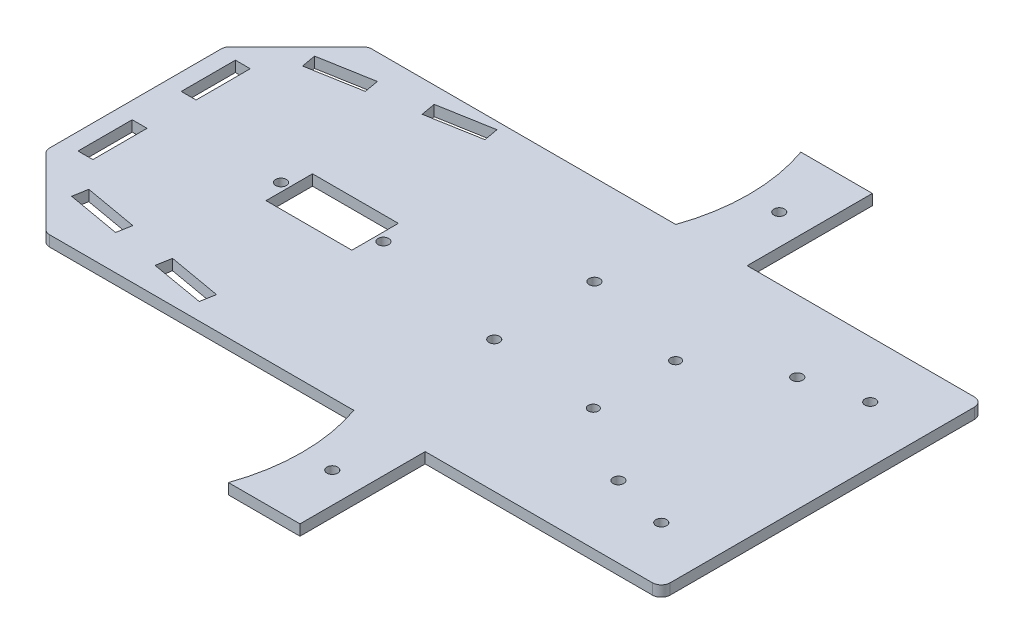
SolidWorks part; units mm, degrees
ref_plane "Front Plane" through (0, 0, 0) normal (0, 0, 1) x (1, 0, 0)
ref_plane "Top Plane" through (0, 0, 0) normal (0, 1, 0) x (1, 0, 0)
ref_plane "Right Plane" through (0, 0, 0) normal (1, 0, 0) x (0, 0, -1)
sketch "Sketch1" plane through (0, 0, 0) normal (0, 1, 0) x (1, 0, 0)
  line L1 (0, 0) -> (192, 0)
  line L2 (0, 0) -> (0, 90)
  line L3 (0, 90) -> (192, 90)
  line L4 (192, 0) -> (192, 90)
  dimension "D1" = 192
  dimension "D2" = 90
extrude "Boss-Extrude1" add sketch "Sketch1" along normal blind 3
sketch "Sketch3" plane through (0, 3, 0) normal (0, 1, 0) x (1, 0, 0)
  line L5 (126, 90) -> (106, 90)
  line L6 (126, 90) -> (126, 125)
  line L7 (126, 125) -> (106, 125)
  line L8 (106, 90) -> (106, 125)
  dimension "D1" = 35
  dimension "D2" = 20
extrude "Boss-Extrude2" add sketch "Sketch3" against normal blind 3
sketch "Sketch4" plane through (0, 3, 0) normal (0, 1, 0) x (1, 0, 0)
  line L2 (106, 125) -> (106, 89.875)
  arc A0 (106, 125) -> (106, 89.875) centre (56.0932, 107.4375) cw
extrude "Cut-Extrude1" cut sketch "Sketch4" against normal blind 5
ref_plane "Plane1" through (0, 0, -45) normal (0, 0, 1) x (1, 0, 0)
mirror "Mirror1" about plane through (0, 0, -45) normal (0, 0, 1) of "Cut-Extrude1", "Boss-Extrude2"
sketch "Sketch5" plane through (0, 3, 0) normal (0, 1, 0) x (1, 0, 0)
  circle A0 centre (139, 57) radius 1.4
  circle A1 centre (139, 34) radius 1.4
  dimension "D1" = 2.8
  dimension "D5" = 2.8
  dimension "D2" = 23
extrude "Cut-Extrude2" cut sketch "Sketch5" against normal blind 5 contours A0
sketch "Sketch6" plane through (0, 3, 0) normal (0, 1, 0) x (1, 0, 0)
  circle A0 centre (139, 34) radius 1.4
  dimension "D2" = 2.8
extrude "Cut-Extrude3" cut sketch "Sketch6" against normal blind 5
sketch "Sketch7" plane through (0, 3, 0) normal (0, 1, 0) x (1, 0, 0)
  line L3 (67, 51.5) -> (43, 51.5)
  line L4 (67, 51.5) -> (67, 38.5)
  line L5 (67, 38.5) -> (43, 38.5)
  line L6 (43, 51.5) -> (43, 38.5)
  circle A0 centre (40.7, 45) radius 1.5
  circle A1 centre (69.3, 45) radius 1.5
  dimension "D5" = 3
  dimension "D6" = 3
  dimension "D2" = 13
  dimension "D3" = 24
extrude "Cut-Extrude4" cut sketch "Sketch7" against normal blind 5
sketch "Sketch8" plane through (0, 3, 0) normal (0, 1, 0) x (1, 0, 0)
  circle A0 centre (160, 20) radius 1.5
  circle A1 centre (160, 70) radius 1.5
  dimension "D3" = 3
  dimension "D4" = 3
extrude "Cut-Extrude5" cut sketch "Sketch8" against normal blind 5000
sketch "Sketch10" plane through (0, 3, 0) normal (0, 1, 0) x (1, 0, 0)
  line L0 (106, 0.125) -> (126, 0) construction
  line L1 (126, -17.5) -> (109, -17.4375) construction
  line L2 (126, 0) -> (126, -35) construction
  line L3 (106, 90) -> (126, 90) construction
  line L4 (126, 107.5) -> (109, 107.4375) construction
  line L5 (126, 90) -> (126, 125) construction
  arc A0 (106, -35) -> (106, 0.125) centre (56.0932, -17.4375) ccw construction
  circle A1 centre (117.5, -17.4688) radius 1.5
  arc A2 (106, 89.875) -> (106, 125) centre (56.0932, 107.4375) ccw construction
  circle A3 centre (117.5, 107.4688) radius 1.5
extrude "Cut-Extrude6" cut sketch "Sketch10" against normal through all
sketch "Sketch11" plane through (0, 3, 0) normal (0, 1, 0) x (1, 0, 0)
  line L0 (192, 90) -> (192, 74.2) construction
  line L1 (192, 0) -> (192, 90) construction
  line L2 (192, 74.2) -> (177.7, 74.2) construction
  line L3 (192, 90) -> (126, 90) construction
  line L4 (126, 0) -> (192, 0) construction
  circle A0 centre (176.2, 74.2) radius 1.5
  circle A1 centre (176.2, 15.8) radius 1.5
  dimension "D1" = 15.8
  dimension "D5" = 3
  dimension "D2" = 15.8
  dimension "D3" = 15.8
  dimension "D4" = 15.8
extrude "Cut-Extrude7" cut sketch "Sketch11" against normal through all
sketch "Sketch13" plane through (0, 3, 0) normal (0, 1, 0) x (1, 0, 0)
  line L0 (160.1799, 90) -> (160, 71.5) construction
  line L1 (192, 90) -> (126, 90) construction
  line L2 (126, 0) -> (192, 0) construction
  line L3 (160, 18.5) -> (160, 0) construction
  line L4 (161.5, 20) -> (107, 20) construction
  line L5 (161.5, 70) -> (107, 70) construction
  line L6 (0, 0) -> (106, 0) construction
  line L7 (106, 90) -> (0, 90) construction
  circle A0 centre (160, 70) radius 1.5 construction
  circle A1 centre (160, 20) radius 1.5 construction
  circle A2 centre (108.5, 36.8) radius 1.5
  circle A3 centre (108.5, 64.8) radius 1.5
  dimension "D1" = 1.5
  dimension "D3" = 28
  dimension "D7" = 16.8
  dimension "D2" = 1.5
  dimension "D4" = 36.8
  dimension "D5" = 25.2
  dimension "D6" = 54.5
extrude "Cut-Extrude9" cut sketch "Sketch13" against normal through all
sketch "Sketch18" plane through (0, 3, 0) normal (0, 1, 0) x (1, 0, 0)
  line L40 (8.865, 24.2336) -> (4.715, 24.2336)
  line L41 (8.865, 24.2336) -> (8.865, 39.3836)
  line L42 (8.865, 39.3836) -> (4.715, 39.3836)
  line L43 (4.715, 24.2336) -> (4.715, 39.3836)
  line L48 (8.865, 68.2336) -> (4.715, 68.2336)
  line L49 (8.865, 68.2336) -> (8.865, 53.0836)
  line L50 (8.865, 53.0836) -> (4.715, 53.0836)
  line L51 (4.715, 68.2336) -> (4.715, 53.0836)
  line L54 (14.7973, 80.2799) -> (29.7171, 82.9107)
  line L55 (29.7171, 82.9107) -> (30.4377, 78.8238)
  line L56 (30.4377, 78.8238) -> (15.5179, 76.193)
  line L57 (15.5179, 76.193) -> (14.7973, 80.2799)
  line L63 (58.1151, 87.9494) -> (43.1953, 85.3187)
  line L64 (43.1953, 85.3187) -> (43.9159, 81.2317)
  line L65 (43.9159, 81.2317) -> (58.8358, 83.8625)
  line L66 (58.8358, 83.8625) -> (58.1151, 87.9494)
  line L71 (15.4918, 16.4762) -> (30.4117, 13.8454)
  line L72 (30.4117, 13.8454) -> (29.691, 9.7584)
  line L73 (29.691, 9.7584) -> (14.7712, 12.3892)
  line L74 (14.7712, 12.3892) -> (15.4918, 16.4762)
  line L79 (58.8234, 8.8356) -> (43.9037, 11.4664)
  line L80 (43.9037, 11.4664) -> (43.1707, 7.3092)
  line L81 (43.1707, 7.3092) -> (58.1027, 4.7487)
  line L82 (58.1027, 4.7487) -> (58.8234, 8.8356)
  dimension "D13" = 15.15
  dimension "D14" = 4.15
  dimension "D15" = 15.15
  dimension "D16" = 4.15
  dimension "D17" = 15.15
  dimension "D18" = 4.15
  dimension "D21" = 15.15
  dimension "D22" = 4.15
  dimension "D23" = 15.15
  dimension "D24" = 4.15
  dimension "D25" = 15.15
  dimension "D26" = 4.15
extrude "Cut-Extrude10" cut sketch "Sketch18" against normal blind 10
sketch "Sketch19" plane through (0, 3, 0) normal (0, 1, 0) x (1, 0, 0)
  line L0 (0, 90) -> (20, 90)
  line L1 (106, 90) -> (0, 90) construction
  line L2 (20, 90) -> (0, 70)
  line L3 (0, 90) -> (0, 0) construction
  line L4 (0, 70) -> (0, 90)
  line L5 (0, 0) -> (0, 20)
  line L6 (0, 20) -> (20, 0)
  line L7 (0, 0) -> (106, 0) construction
  line L8 (20, 0) -> (0, 0)
  dimension "D1" = 20
  dimension "D2" = 20
  dimension "D3" = 20
  dimension "D4" = 20
extrude "Cut-Extrude11" cut sketch "Sketch19" against normal blind 10
fillet "Fillet1" radius 2.5 6 edges at (192, 1.5, 0) (192, 1.5, -90) (20, 1.5, 0) (0, 1.5, -20) (20, 1.5, -90) (0, 1.5, -70)
